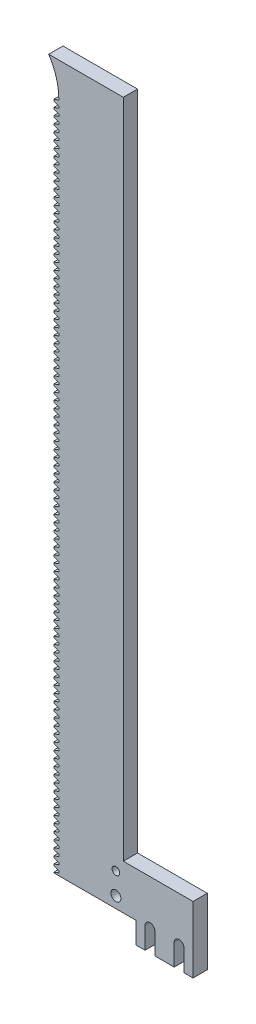
SolidWorks part; units mm, degrees
ref_plane "Front Plane" through (0, 0, 0) normal (0, 0, 1) x (1, 0, 0)
ref_plane "Top Plane" through (0, 0, 0) normal (0, 1, 0) x (1, 0, 0)
ref_plane "Right Plane" through (0, 0, 0) normal (1, 0, 0) x (0, 0, -1)
sketch "Sketch1" plane through (0, 0, 0) normal (0, 0, 1) x (1, 0, 0)
  line L0 (-9.5, -73.594) -> (-8.375, -74.0034)
  line L1 (-9, -75) -> (9, -75) construction
  line L2 (-9, -75) -> (-9, 75) construction
  line L3 (-9, 75) -> (9, 75) construction
  line L4 (9, -75) -> (9, 75) construction
  line L5 (-9, -75) -> (9, 75) construction
  line L6 (-9, 75) -> (9, -75) construction
  line L7 (-8.375, -74.0034) -> (-8.375, -74.4479)
  line L8 (-8.375, -74.4479) -> (-9.5, -74.8573)
  line L9 (-9.5, -74.8573) -> (-9.5, -75)
  line L10 (-9.5, -75) -> (9, -75)
  line L11 (9, -75) -> (9, 75)
  line L12 (9, 75) -> (-8.375, 75)
  line L13 (-8.375, 75) -> (-8.375, 74.7778)
  line L14 (-8.375, 74.7778) -> (-9.5, 74.3683)
  line L15 (-9.5, 74.3683) -> (-9.5, 74.0609)
  line L16 (-9.5, 74.0609) -> (-8.375, 73.6514)
  line L17 (-8.375, 73.6514) -> (-8.375, 73.207)
  line L18 (-8.375, 73.207) -> (-9.5, 72.7975)
  line L19 (-9.5, 72.7975) -> (-9.5, 72.4901)
  line L20 (-9.5, 72.4901) -> (-8.375, 72.0806)
  line L21 (-8.375, 72.0806) -> (-8.375, 71.6362)
  line L22 (-8.375, 71.6362) -> (-9.5, 71.2267)
  line L23 (-9.5, 71.2267) -> (-9.5, 70.9193)
  line L24 (-9.5, 70.9193) -> (-8.375, 70.5098)
  line L25 (-8.375, 70.5098) -> (-8.375, 70.0654)
  line L26 (-8.375, 70.0654) -> (-9.5, 69.6559)
  line L27 (-9.5, 69.6559) -> (-9.5, 69.3485)
  line L28 (-9.5, 69.3485) -> (-8.375, 68.939)
  line L29 (-8.375, 68.939) -> (-8.375, 68.4946)
  line L30 (-8.375, 68.4946) -> (-9.5, 68.0851)
  line L31 (-9.5, 68.0851) -> (-9.5, 67.7777)
  line L32 (-9.5, 67.7777) -> (-8.375, 67.3682)
  line L33 (-8.375, 67.3682) -> (-8.375, 66.9238)
  line L34 (-8.375, 66.9238) -> (-9.5, 66.5143)
  line L35 (-9.5, 66.5143) -> (-9.5, 66.2069)
  line L36 (-9.5, 66.2069) -> (-8.375, 65.7974)
  line L37 (-8.375, 65.7974) -> (-8.375, 65.353)
  line L38 (-8.375, 65.353) -> (-9.5, 64.9435)
  line L39 (-9.5, 64.9435) -> (-9.5, 64.6361)
  line L40 (-9.5, 64.6361) -> (-8.375, 64.2266)
  line L41 (-8.375, 64.2266) -> (-8.375, 63.7822)
  line L42 (-8.375, 63.7822) -> (-9.5, 63.3727)
  line L43 (-9.5, 63.3727) -> (-9.5, 63.0653)
  line L44 (-9.5, 63.0653) -> (-8.375, 62.6558)
  line L45 (-8.375, 62.6558) -> (-8.375, 62.2114)
  line L46 (-8.375, 62.2114) -> (-9.5, 61.8019)
  line L47 (-9.5, 61.8019) -> (-9.5, 61.4945)
  line L48 (-9.5, 61.4945) -> (-8.375, 61.0851)
  line L49 (-8.375, 61.0851) -> (-8.375, 60.6406)
  line L50 (-8.375, 60.6406) -> (-9.5, 60.2311)
  line L51 (-9.5, 60.2311) -> (-9.5, 59.9237)
  line L52 (-9.5, 59.9237) -> (-8.375, 59.5143)
  line L53 (-8.375, 59.5143) -> (-8.375, 59.0698)
  line L54 (-8.375, 59.0698) -> (-9.5, 58.6604)
  line L55 (-9.5, 58.6604) -> (-9.5, 58.3529)
  line L56 (-9.5, 58.3529) -> (-8.375, 57.9435)
  line L57 (-8.375, 57.9435) -> (-8.375, 57.499)
  line L58 (-8.375, 57.499) -> (-9.5, 57.0896)
  line L59 (-9.5, 57.0896) -> (-9.5, 56.7821)
  line L60 (-9.5, 56.7821) -> (-8.375, 56.3727)
  line L61 (-8.375, 56.3727) -> (-8.375, 55.9282)
  line L62 (-8.375, 55.9282) -> (-9.5, 55.5188)
  line L63 (-9.5, 55.5188) -> (-9.5, 55.2113)
  line L64 (-9.5, 55.2113) -> (-8.375, 54.8019)
  line L65 (-8.375, 54.8019) -> (-8.375, 54.3574)
  line L66 (-8.375, 54.3574) -> (-9.5, 53.948)
  line L67 (-9.5, 53.948) -> (-9.5, 53.6405)
  line L68 (-9.5, 53.6405) -> (-8.375, 53.2311)
  line L69 (-8.375, 53.2311) -> (-8.375, 52.7866)
  line L70 (-8.375, 52.7866) -> (-9.5, 52.3772)
  line L71 (-9.5, 52.3772) -> (-9.5, 52.0697)
  line L72 (-9.5, 52.0697) -> (-8.375, 51.6603)
  line L73 (-8.375, 51.6603) -> (-8.375, 51.2158)
  line L74 (-8.375, 51.2158) -> (-9.5, 50.8064)
  line L75 (-9.5, 50.8064) -> (-9.5, 50.4989)
  line L76 (-9.5, 50.4989) -> (-8.375, 50.0895)
  line L77 (-8.375, 50.0895) -> (-8.375, 49.645)
  line L78 (-8.375, 49.645) -> (-9.5, 49.2356)
  line L79 (-9.5, 49.2356) -> (-9.5, 48.9281)
  line L80 (-9.5, 48.9281) -> (-8.375, 48.5187)
  line L81 (-8.375, 48.5187) -> (-8.375, 48.0742)
  line L82 (-8.375, 48.0742) -> (-9.5, 47.6648)
  line L83 (-9.5, 47.6648) -> (-9.5, 47.3574)
  line L84 (-9.5, 47.3574) -> (-8.375, 46.9479)
  line L85 (-8.375, 46.9479) -> (-8.375, 46.5034)
  line L86 (-8.375, 46.5034) -> (-9.5, 46.094)
  line L87 (-9.5, 46.094) -> (-9.5, 45.7866)
  line L88 (-9.5, 45.7866) -> (-8.375, 45.3771)
  line L89 (-8.375, 45.3771) -> (-8.375, 44.9327)
  line L90 (-8.375, 44.9327) -> (-9.5, 44.5232)
  line L91 (-9.5, 44.5232) -> (-9.5, 44.2158)
  line L92 (-9.5, 44.2158) -> (-8.375, 43.8063)
  line L93 (-8.375, 43.8063) -> (-8.375, 43.3619)
  line L94 (-8.375, 43.3619) -> (-9.5, 42.9524)
  line L95 (-9.5, 42.9524) -> (-9.5, 42.645)
  line L96 (-9.5, 42.645) -> (-8.375, 42.2355)
  line L97 (-8.375, 42.2355) -> (-8.375, 41.7911)
  line L98 (-8.375, 41.7911) -> (-9.5, 41.3816)
  line L99 (-9.5, 41.3816) -> (-9.5, 41.0742)
  line L100 (-9.5, 41.0742) -> (-8.375, 40.6647)
  line L101 (-8.375, 40.6647) -> (-8.375, 40.2203)
  line L102 (-8.375, 40.2203) -> (-9.5, 39.8108)
  line L103 (-9.5, 39.8108) -> (-9.5, 39.5034)
  line L104 (-9.5, 39.5034) -> (-8.375, 39.0939)
  line L105 (-8.375, 39.0939) -> (-8.375, 38.6495)
  line L106 (-8.375, 38.6495) -> (-9.5, 38.24)
  line L107 (-9.5, 38.24) -> (-9.5, 37.9326)
  line L108 (-9.5, 37.9326) -> (-8.375, 37.5231)
  line L109 (-8.375, 37.5231) -> (-8.375, 37.0787)
  line L110 (-8.375, 37.0787) -> (-9.5, 36.6692)
  line L111 (-9.5, 36.6692) -> (-9.5, 36.3618)
  line L112 (-9.5, 36.3618) -> (-8.375, 35.9523)
  line L113 (-8.375, 35.9523) -> (-8.375, 35.5079)
  line L114 (-8.375, 35.5079) -> (-9.5, 35.0984)
  line L115 (-9.5, 35.0984) -> (-9.5, 34.791)
  line L116 (-9.5, 34.791) -> (-8.375, 34.3815)
  line L117 (-8.375, 34.3815) -> (-8.375, 33.9371)
  line L118 (-8.375, 33.9371) -> (-9.5, 33.5276)
  line L119 (-9.5, 33.5276) -> (-9.5, 33.2202)
  line L120 (-9.5, 33.2202) -> (-8.375, 32.8107)
  line L121 (-8.375, 32.8107) -> (-8.375, 32.3663)
  line L122 (-8.375, 32.3663) -> (-9.5, 31.9568)
  line L123 (-9.5, 31.9568) -> (-9.5, 31.6494)
  line L124 (-9.5, 31.6494) -> (-8.375, 31.2399)
  line L125 (-8.375, 31.2399) -> (-8.375, 30.7955)
  line L126 (-8.375, 30.7955) -> (-9.5, 30.386)
  line L127 (-9.5, 30.386) -> (-9.5, 30.0786)
  line L128 (-9.5, 30.0786) -> (-8.375, 29.6691)
  line L129 (-8.375, 29.6691) -> (-8.375, 29.2247)
  line L130 (-8.375, 29.2247) -> (-9.5, 28.8152)
  line L131 (-9.5, 28.8152) -> (-9.5, 28.5078)
  line L132 (-9.5, 28.5078) -> (-8.375, 28.0983)
  line L133 (-8.375, 28.0983) -> (-8.375, 27.6539)
  line L134 (-8.375, 27.6539) -> (-9.5, 27.2444)
  line L135 (-9.5, 27.2444) -> (-9.5, 26.937)
  line L136 (-9.5, 26.937) -> (-8.375, 26.5275)
  line L137 (-8.375, 26.5275) -> (-8.375, 26.0831)
  line L138 (-8.375, 26.0831) -> (-9.5, 25.6736)
  line L139 (-9.5, 25.6736) -> (-9.5, 25.3662)
  line L140 (-9.5, 25.3662) -> (-8.375, 24.9567)
  line L141 (-8.375, 24.9567) -> (-8.375, 24.5123)
  line L142 (-8.375, 24.5123) -> (-9.5, 24.1028)
  line L143 (-9.5, 24.1028) -> (-9.5, 23.7954)
  line L144 (-9.5, 23.7954) -> (-8.375, 23.3859)
  line L145 (-8.375, 23.3859) -> (-8.375, 22.9415)
  line L146 (-8.375, 22.9415) -> (-9.5, 22.532)
  line L147 (-9.5, 22.532) -> (-9.5, 22.2246)
  line L148 (-9.5, 22.2246) -> (-8.375, 21.8151)
  line L149 (-8.375, 21.8151) -> (-8.375, 21.3707)
  line L150 (-8.375, 21.3707) -> (-9.5, 20.9612)
  line L151 (-9.5, 20.9612) -> (-9.5, 20.6538)
  line L152 (-9.5, 20.6538) -> (-8.375, 20.2443)
  line L153 (-8.375, 20.2443) -> (-8.375, 19.7999)
  line L154 (-8.375, 19.7999) -> (-9.5, 19.3904)
  line L155 (-9.5, 19.3904) -> (-9.5, 19.083)
  line L156 (-9.5, 19.083) -> (-8.375, 18.6735)
  line L157 (-8.375, 18.6735) -> (-8.375, 18.2291)
  line L158 (-8.375, 18.2291) -> (-9.5, 17.8196)
  line L159 (-9.5, 17.8196) -> (-9.5, 17.5122)
  line L160 (-9.5, 17.5122) -> (-8.375, 17.1028)
  line L161 (-8.375, 17.1028) -> (-8.375, 16.6583)
  line L162 (-8.375, 16.6583) -> (-9.5, 16.2489)
  line L163 (-9.5, 16.2489) -> (-9.5, 15.9414)
  line L164 (-9.5, 15.9414) -> (-8.375, 15.532)
  line L165 (-8.375, 15.532) -> (-8.375, 15.0875)
  line L166 (-8.375, 15.0875) -> (-9.5, 14.6781)
  line L167 (-9.5, 14.6781) -> (-9.5, 14.3706)
  line L168 (-9.5, 14.3706) -> (-8.375, 13.9612)
  line L169 (-8.375, 13.9612) -> (-8.375, 13.5167)
  line L170 (-8.375, 13.5167) -> (-9.5, 13.1073)
  line L171 (-9.5, 13.1073) -> (-9.5, 12.7998)
  line L172 (-9.5, 12.7998) -> (-8.375, 12.3904)
  line L173 (-8.375, 12.3904) -> (-8.375, 11.9459)
  line L174 (-8.375, 11.9459) -> (-9.5, 11.5365)
  line L175 (-9.5, 11.5365) -> (-9.5, 11.229)
  line L176 (-9.5, 11.229) -> (-8.375, 10.8196)
  line L177 (-8.375, 10.8196) -> (-8.375, 10.3751)
  line L178 (-8.375, 10.3751) -> (-9.5, 9.9657)
  line L179 (-9.5, 9.9657) -> (-9.5, 9.6582)
  line L180 (-9.5, 9.6582) -> (-8.375, 9.2488)
  line L181 (-8.375, 9.2488) -> (-8.375, 8.8043)
  line L182 (-8.375, 8.8043) -> (-9.5, 8.3949)
  line L183 (-9.5, 8.3949) -> (-9.5, 8.0874)
  line L184 (-9.5, 8.0874) -> (-8.375, 7.678)
  line L185 (-8.375, 7.678) -> (-8.375, 7.2335)
  line L186 (-8.375, 7.2335) -> (-9.5, 6.8241)
  line L187 (-9.5, 6.8241) -> (-9.5, 6.5166)
  line L188 (-9.5, 6.5166) -> (-8.375, 6.1072)
  line L189 (-8.375, 6.1072) -> (-8.375, 5.6627)
  line L190 (-8.375, 5.6627) -> (-9.5, 5.2533)
  line L191 (-9.5, 5.2533) -> (-9.5, 4.9458)
  line L192 (-9.5, 4.9458) -> (-8.375, 4.5364)
  line L193 (-8.375, 4.5364) -> (-8.375, 4.0919)
  line L194 (-8.375, 4.0919) -> (-9.5, 3.6825)
  line L195 (-9.5, 3.6825) -> (-9.5, 3.3751)
  line L196 (-9.5, 3.3751) -> (-8.375, 2.9656)
  line L197 (-8.375, 2.9656) -> (-8.375, 2.5212)
  line L198 (-8.375, 2.5212) -> (-9.5, 2.1117)
  line L199 (-9.5, 2.1117) -> (-9.5, 1.8043)
  line L200 (-9.5, 1.8043) -> (-8.375, 1.3948)
  line L201 (-8.375, 1.3948) -> (-8.375, 0.9504)
  line L202 (-8.375, 0.9504) -> (-9.5, 0.5409)
  line L203 (-9.5, 0.5409) -> (-9.5, 0.2335)
  line L204 (-9.5, 0.2335) -> (-8.375, -0.176)
  line L205 (-8.375, -0.176) -> (-8.375, -0.6204)
  line L206 (-8.375, -0.6204) -> (-9.5, -1.0299)
  line L207 (-9.5, -1.0299) -> (-9.5, -1.3373)
  line L208 (-9.5, -1.3373) -> (-8.375, -1.7468)
  line L209 (-8.375, -1.7468) -> (-8.375, -2.1912)
  line L210 (-8.375, -2.1912) -> (-9.5, -2.6007)
  line L211 (-9.5, -2.6007) -> (-9.5, -2.9081)
  line L212 (-9.5, -2.9081) -> (-8.375, -3.3176)
  line L213 (-8.375, -3.3176) -> (-8.375, -3.762)
  line L214 (-8.375, -3.762) -> (-9.5, -4.1715)
  line L215 (-9.5, -4.1715) -> (-9.5, -4.4789)
  line L216 (-9.5, -4.4789) -> (-8.375, -4.8884)
  line L217 (-8.375, -4.8884) -> (-8.375, -5.3328)
  line L218 (-8.375, -5.3328) -> (-9.5, -5.7423)
  line L219 (-9.5, -5.7423) -> (-9.5, -6.0497)
  line L220 (-9.5, -6.0497) -> (-8.375, -6.4592)
  line L221 (-8.375, -6.4592) -> (-8.375, -6.9036)
  line L222 (-8.375, -6.9036) -> (-9.5, -7.3131)
  line L223 (-9.5, -7.3131) -> (-9.5, -7.6205)
  line L224 (-9.5, -7.6205) -> (-8.375, -8.03)
  line L225 (-8.375, -8.03) -> (-8.375, -8.4744)
  line L226 (-8.375, -8.4744) -> (-9.5, -8.8839)
  line L227 (-9.5, -8.8839) -> (-9.5, -9.1913)
  line L228 (-9.5, -9.1913) -> (-8.375, -9.6008)
  line L229 (-8.375, -9.6008) -> (-8.375, -10.0452)
  line L230 (-8.375, -10.0452) -> (-9.5, -10.4547)
  line L231 (-9.5, -10.4547) -> (-9.5, -10.7621)
  line L232 (-9.5, -10.7621) -> (-8.375, -11.1716)
  line L233 (-8.375, -11.1716) -> (-8.375, -11.616)
  line L234 (-8.375, -11.616) -> (-9.5, -12.0255)
  line L235 (-9.5, -12.0255) -> (-9.5, -12.3329)
  line L236 (-9.5, -12.3329) -> (-8.375, -12.7424)
  line L237 (-8.375, -12.7424) -> (-8.375, -13.1868)
  line L238 (-8.375, -13.1868) -> (-9.5, -13.5963)
  line L239 (-9.5, -13.5963) -> (-9.5, -13.9037)
  line L240 (-9.5, -13.9037) -> (-8.375, -14.3132)
  line L241 (-8.375, -14.3132) -> (-8.375, -14.7576)
  line L242 (-8.375, -14.7576) -> (-9.5, -15.1671)
  line L243 (-9.5, -15.1671) -> (-9.5, -15.4745)
  line L244 (-9.5, -15.4745) -> (-8.375, -15.884)
  line L245 (-8.375, -15.884) -> (-8.375, -16.3284)
  line L246 (-8.375, -16.3284) -> (-9.5, -16.7379)
  line L247 (-9.5, -16.7379) -> (-9.5, -17.0453)
  line L248 (-9.5, -17.0453) -> (-8.375, -17.4548)
  line L249 (-8.375, -17.4548) -> (-8.375, -17.8992)
  line L250 (-8.375, -17.8992) -> (-9.5, -18.3087)
  line L251 (-9.5, -18.3087) -> (-9.5, -18.6161)
  line L252 (-9.5, -18.6161) -> (-8.375, -19.0256)
  line L253 (-8.375, -19.0256) -> (-8.375, -19.47)
  line L254 (-8.375, -19.47) -> (-9.5, -19.8795)
  line L255 (-9.5, -19.8795) -> (-9.5, -20.1869)
  line L256 (-9.5, -20.1869) -> (-8.375, -20.5964)
  line L257 (-8.375, -20.5964) -> (-8.375, -21.0408)
  line L258 (-8.375, -21.0408) -> (-9.5, -21.4503)
  line L259 (-9.5, -21.4503) -> (-9.5, -21.7577)
  line L260 (-9.5, -21.7577) -> (-8.375, -22.1672)
  line L261 (-8.375, -22.1672) -> (-8.375, -22.6116)
  line L262 (-8.375, -22.6116) -> (-9.5, -23.0211)
  line L263 (-9.5, -23.0211) -> (-9.5, -23.3285)
  line L264 (-9.5, -23.3285) -> (-8.375, -23.738)
  line L265 (-8.375, -23.738) -> (-8.375, -24.1824)
  line L266 (-8.375, -24.1824) -> (-9.5, -24.5919)
  line L267 (-9.5, -24.5919) -> (-9.5, -24.8993)
  line L268 (-9.5, -24.8993) -> (-8.375, -25.3087)
  line L269 (-8.375, -25.3087) -> (-8.375, -25.7532)
  line L270 (-8.375, -25.7532) -> (-9.5, -26.1626)
  line L271 (-9.5, -26.1626) -> (-9.5, -26.4701)
  line L272 (-9.5, -26.4701) -> (-8.375, -26.8795)
  line L273 (-8.375, -26.8795) -> (-8.375, -27.324)
  line L274 (-8.375, -27.324) -> (-9.5, -27.7334)
  line L275 (-9.5, -27.7334) -> (-9.5, -28.0409)
  line L276 (-9.5, -28.0409) -> (-8.375, -28.4503)
  line L277 (-8.375, -28.4503) -> (-8.375, -28.8948)
  line L278 (-8.375, -28.8948) -> (-9.5, -29.3042)
  line L279 (-9.5, -29.3042) -> (-9.5, -29.6117)
  line L280 (-9.5, -29.6117) -> (-8.375, -30.0211)
  line L281 (-8.375, -30.0211) -> (-8.375, -30.4656)
  line L282 (-8.375, -30.4656) -> (-9.5, -30.875)
  line L283 (-9.5, -30.875) -> (-9.5, -31.1825)
  line L284 (-9.5, -31.1825) -> (-8.375, -31.5919)
  line L285 (-8.375, -31.5919) -> (-8.375, -32.0364)
  line L286 (-8.375, -32.0364) -> (-9.5, -32.4458)
  line L287 (-9.5, -32.4458) -> (-9.5, -32.7533)
  line L288 (-9.5, -32.7533) -> (-8.375, -33.1627)
  line L289 (-8.375, -33.1627) -> (-8.375, -33.6072)
  line L290 (-8.375, -33.6072) -> (-9.5, -34.0166)
  line L291 (-9.5, -34.0166) -> (-9.5, -34.3241)
  line L292 (-9.5, -34.3241) -> (-8.375, -34.7335)
  line L293 (-8.375, -34.7335) -> (-8.375, -35.178)
  line L294 (-8.375, -35.178) -> (-9.5, -35.5874)
  line L295 (-9.5, -35.5874) -> (-9.5, -35.8949)
  line L296 (-9.5, -35.8949) -> (-8.375, -36.3043)
  line L297 (-8.375, -36.3043) -> (-8.375, -36.7488)
  line L298 (-8.375, -36.7488) -> (-9.5, -37.1582)
  line L299 (-9.5, -37.1582) -> (-9.5, -37.4657)
  line L300 (-9.5, -37.4657) -> (-8.375, -37.8751)
  line L301 (-8.375, -37.8751) -> (-8.375, -38.3196)
  line L302 (-8.375, -38.3196) -> (-9.5, -38.729)
  line L303 (-9.5, -38.729) -> (-9.5, -39.0364)
  line L304 (-9.5, -39.0364) -> (-8.375, -39.4459)
  line L305 (-8.375, -39.4459) -> (-8.375, -39.8903)
  line L306 (-8.375, -39.8903) -> (-9.5, -40.2998)
  line L307 (-9.5, -40.2998) -> (-9.5, -40.6072)
  line L308 (-9.5, -40.6072) -> (-8.375, -41.0167)
  line L309 (-8.375, -41.0167) -> (-8.375, -41.4611)
  line L310 (-8.375, -41.4611) -> (-9.5, -41.8706)
  line L311 (-9.5, -41.8706) -> (-9.5, -42.178)
  line L312 (-9.5, -42.178) -> (-8.375, -42.5875)
  line L313 (-8.375, -42.5875) -> (-8.375, -43.0319)
  line L314 (-8.375, -43.0319) -> (-9.5, -43.4414)
  line L315 (-9.5, -43.4414) -> (-9.5, -43.7488)
  line L316 (-9.5, -43.7488) -> (-8.375, -44.1583)
  line L317 (-8.375, -44.1583) -> (-8.375, -44.6027)
  line L318 (-8.375, -44.6027) -> (-9.5, -45.0122)
  line L319 (-9.5, -45.0122) -> (-9.5, -45.3196)
  line L320 (-9.5, -45.3196) -> (-8.375, -45.7291)
  line L321 (-8.375, -45.7291) -> (-8.375, -46.1735)
  line L322 (-8.375, -46.1735) -> (-9.5, -46.583)
  line L323 (-9.5, -46.583) -> (-9.5, -46.8904)
  line L324 (-9.5, -46.8904) -> (-8.375, -47.2999)
  line L325 (-8.375, -47.2999) -> (-8.375, -47.7443)
  line L326 (-8.375, -47.7443) -> (-9.5, -48.1538)
  line L327 (-9.5, -48.1538) -> (-9.5, -48.4612)
  line L328 (-9.5, -48.4612) -> (-8.375, -48.8707)
  line L329 (-8.375, -48.8707) -> (-8.375, -49.3151)
  line L330 (-8.375, -49.3151) -> (-9.5, -49.7246)
  line L331 (-9.5, -49.7246) -> (-9.5, -50.032)
  line L332 (-9.5, -50.032) -> (-8.375, -50.4415)
  line L333 (-8.375, -50.4415) -> (-8.375, -50.8859)
  line L334 (-8.375, -50.8859) -> (-9.5, -51.2954)
  line L335 (-9.5, -51.2954) -> (-9.5, -51.6028)
  line L336 (-9.5, -51.6028) -> (-8.375, -52.0123)
  line L337 (-8.375, -52.0123) -> (-8.375, -52.4567)
  line L338 (-8.375, -52.4567) -> (-9.5, -52.8662)
  line L339 (-9.5, -52.8662) -> (-9.5, -53.1736)
  line L340 (-9.5, -53.1736) -> (-8.375, -53.5831)
  line L341 (-8.375, -53.5831) -> (-8.375, -54.0275)
  line L342 (-8.375, -54.0275) -> (-9.5, -54.437)
  line L343 (-9.5, -54.437) -> (-9.5, -54.7444)
  line L344 (-9.5, -54.7444) -> (-8.375, -55.1539)
  line L345 (-8.375, -55.1539) -> (-8.375, -55.5983)
  line L346 (-8.375, -55.5983) -> (-9.5, -56.0078)
  line L347 (-9.5, -56.0078) -> (-9.5, -56.3152)
  line L348 (-9.5, -56.3152) -> (-8.375, -56.7247)
  line L349 (-8.375, -56.7247) -> (-8.375, -57.1691)
  line L350 (-8.375, -57.1691) -> (-9.5, -57.5786)
  line L351 (-9.5, -57.5786) -> (-9.5, -57.886)
  line L352 (-9.5, -57.886) -> (-8.375, -58.2955)
  line L353 (-8.375, -58.2955) -> (-8.375, -58.7399)
  line L354 (-8.375, -58.7399) -> (-9.5, -59.1494)
  line L355 (-9.5, -59.1494) -> (-9.5, -59.4568)
  line L356 (-9.5, -59.4568) -> (-8.375, -59.8663)
  line L357 (-8.375, -59.8663) -> (-8.375, -60.3107)
  line L358 (-8.375, -60.3107) -> (-9.5, -60.7202)
  line L359 (-9.5, -60.7202) -> (-9.5, -61.0276)
  line L360 (-9.5, -61.0276) -> (-8.375, -61.4371)
  line L361 (-8.375, -61.4371) -> (-8.375, -61.8815)
  line L362 (-8.375, -61.8815) -> (-9.5, -62.291)
  line L363 (-9.5, -62.291) -> (-9.5, -62.5984)
  line L364 (-9.5, -62.5984) -> (-8.375, -63.0079)
  line L365 (-8.375, -63.0079) -> (-8.375, -63.4523)
  line L366 (-8.375, -63.4523) -> (-9.5, -63.8618)
  line L367 (-9.5, -63.8618) -> (-9.5, -64.1692)
  line L368 (-9.5, -64.1692) -> (-8.375, -64.5787)
  line L369 (-8.375, -64.5787) -> (-8.375, -65.0231)
  line L370 (-8.375, -65.0231) -> (-9.5, -65.4326)
  line L371 (-9.5, -65.4326) -> (-9.5, -65.74)
  line L372 (-9.5, -65.74) -> (-8.375, -66.1495)
  line L373 (-8.375, -66.1495) -> (-8.375, -66.5939)
  line L374 (-8.375, -66.5939) -> (-9.5, -67.0034)
  line L375 (-9.5, -67.0034) -> (-9.5, -67.3108)
  line L376 (-9.5, -67.3108) -> (-8.375, -67.7202)
  line L377 (-8.375, -67.7202) -> (-8.375, -68.1647)
  line L378 (-8.375, -68.1647) -> (-9.5, -68.5741)
  line L379 (-9.5, -68.5741) -> (-9.5, -68.8816)
  line L380 (-9.5, -68.8816) -> (-8.375, -69.291)
  line L381 (-8.375, -69.291) -> (-8.375, -69.7355)
  line L382 (-8.375, -69.7355) -> (-9.5, -70.1449)
  line L383 (-9.5, -70.1449) -> (-9.5, -70.4524)
  line L384 (-9.5, -70.4524) -> (-8.375, -70.8618)
  line L385 (-8.375, -70.8618) -> (-8.375, -71.3063)
  line L386 (-8.375, -71.3063) -> (-9.5, -71.7157)
  line L387 (-9.5, -71.7157) -> (-9.5, -72.0232)
  line L388 (-9.5, -72.0232) -> (-8.375, -72.4326)
  line L389 (-8.375, -72.4326) -> (-8.375, -72.8771)
  line L390 (-8.375, -72.8771) -> (-9.5, -73.2865)
  line L391 (-9.5, -73.2865) -> (-9.5, -73.594)
  line L392 (6, 75) -> (6, -75)
  point P0 (0, 0)
  dimension "D1" = 18
  dimension "D2" = 150
  dimension "D3" = 3
extrude "Boss-Extrude2" add sketch "Sketch1" along normal blind 3.175 contours L392 L12 L13 L14 L15 L16 L17 L18 L19 L20 L21 L22 L23 L24 L25 L26 L27 L28 L29 L30 L31 L32 L33 L34 L35 L36 L37 L38 L39 L40 L41 L42 L43 L44 L45 L46 L47 L48 L49 L50 L51 L52 L53 L54 L55 L56 L57 L58 L59 L60 L61 region at (-1.451, 0.0002, 0)
sketch "Sketch2" plane through (0, 0, 3.175) normal (0, 0, 1) x (1, 0, 0)
  line L0 (-8.375, 75) -> (-8.375, 74.7778) construction
  line L1 (-21.97, 75) -> (-8.375, 75) construction
  line L2 (-10.631, 82.5) -> (6, 82.5)
  line L3 (6, 82.5) -> (6, 75)
  line L4 (6, 75) -> (-8.375, 75) construction
  line L5 (6, 75) -> (-8.375, 75)
  circle A0 centre (-21.97, 75) radius 13.595
  dimension "D1" = 27.1899
  dimension "D2" = 7.5
extrude "Boss-Extrude3" add sketch "Sketch2" against normal blind 3.175 contours A0 L5 L3 L2 region at (-1.5646, 78.8416, 3.175)
sketch "Sketch3" plane through (0, 0, 3.175) normal (0, 0, 1) x (1, 0, 0)
  line L0 (6, 82.5) -> (6, -75) construction
  line L1 (6, -75) -> (21.55, -75)
  line L2 (6, -75) -> (6, -65)
  line L3 (6, -65) -> (21.55, -65)
  line L4 (21.55, -75) -> (21.55, -65)
  line L5 (-9.5, -75) -> (6, -75) construction
  point P8 (0, 0)
  dimension "D1" = 10
  dimension "D2" = 15.55
extrude "Boss-Extrude4" add sketch "Sketch3" against normal blind 3.175
sketch "Sketch4" plane through (0, 0, 3.175) normal (0, 0, 1) x (1, 0, 0)
  line L0 (21.55, -75) -> (21.55, -65)
  line L1 (21.55, -75) -> (21.55, -65) construction
  line L2 (21.55, -75) -> (21.55, -65)
  circle A0 centre (4.35, -72.5) radius 1.125
  circle A1 centre (4.35, -67.71) radius 1.125
  circle A2 centre (4.35, -67.71) radius 0.85
  dimension "D1" = 1.7
extrude "Cut-Extrude1" cut sketch "Sketch4" against normal blind 9.5858 contours A0 | A2 region at (4.35, -72.5, 3.175) region at (4.35, -67.71, 3.175)
sketch "Sketch5" plane through (0, 0, 3.175) normal (0, 0, 1) x (1, 0, 0)
  line L1 (21.55, -75) -> (8.85, -75)
  line L2 (21.55, -75) -> (21.55, -79.779)
  line L3 (21.55, -79.779) -> (8.85, -79.779)
  line L4 (8.85, -75) -> (8.85, -79.779)
  dimension "D1" = 12.7
  dimension "D2" = 4.779
extrude "Boss-Extrude5" add sketch "Sketch5" against normal blind 3.175
sketch "Sketch6" plane through (0, 0, 3.175) normal (0, 0, 1) x (1, 0, 0)
  line L0 (8.85, -79.779) -> (21.55, -79.779) construction
  line L1 (10.85, -79.779) -> (13.05, -79.779)
  line L2 (10.85, -79.779) -> (10.85, -75)
  line L3 (10.85, -75) -> (13.05, -75) construction
  line L4 (13.05, -79.779) -> (13.05, -75)
  line L5 (17.35, -79.779) -> (19.55, -79.779)
  line L6 (17.35, -79.779) -> (17.35, -75)
  line L7 (17.35, -75) -> (19.55, -75) construction
  line L8 (19.55, -79.779) -> (19.55, -75)
  line L9 (-9.5, -75) -> (8.85, -75) construction
  circle A0 centre (18.45, -75) radius 1.1
  circle A1 centre (11.95, -75) radius 1.1
  point P11 (11.95, -79.779)
  point P13 (18.45, -79.779)
  point P18 (0, 0)
  point P21 (0, 0)
  dimension "D1" = 6.5
  dimension "D2" = 2.2
  dimension "D3" = 3.1
  dimension "D4" = 3.1
extrude "Cut-Extrude2" cut sketch "Sketch6" against normal blind 3.175 contours A0 L6 L5 L8 | A0 | A1 L2 L1 L4 | A1 region at (11.95, -77.8138, 3.175) region at (11.95, -75, 3.175) region at (18.45, -77.8138, 3.175) region at (18.45, -75, 3.175)
